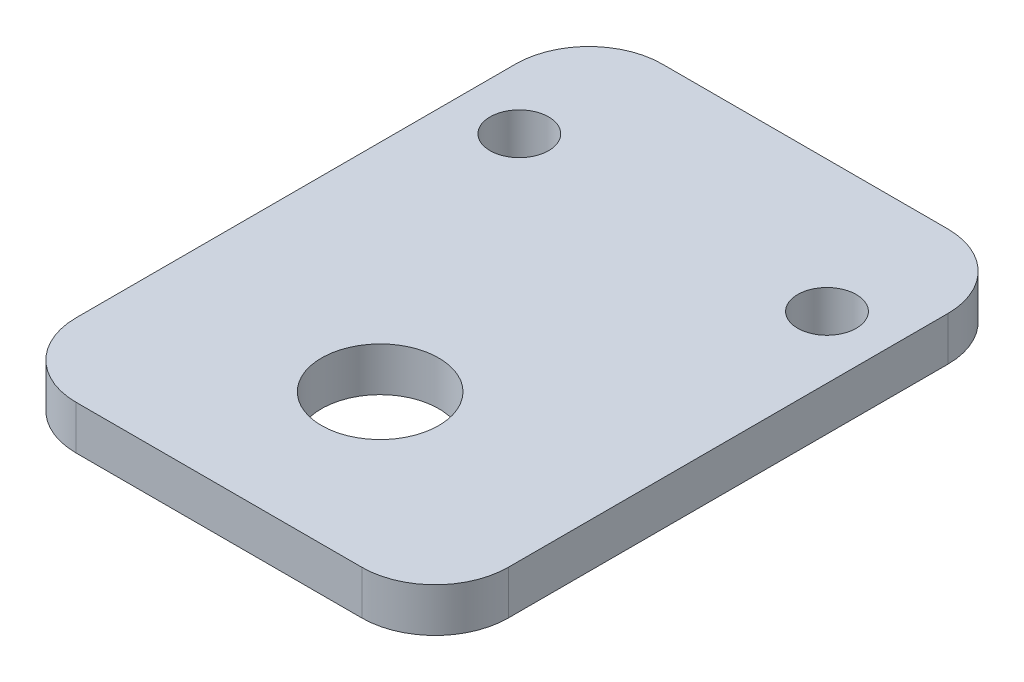
SolidWorks part; units mm, degrees
material "3.0205 (EN-AW 1200)"
ref_plane "Plan de face" through (0, 0, 0) normal (0, 0, 1) x (1, 0, 0)
ref_plane "Plan de dessus" through (0, 0, 0) normal (0, 1, 0) x (1, 0, 0)
ref_plane "Plan de droite" through (0, 0, 0) normal (1, 0, 0) x (0, 0, -1)
sketch "Esquisse1" plane through (0, 0, 0) normal (0, 0, 1) x (1, 0, 0)
  line L1 (0, 0) -> (29.5, 0)
  dimension "D2" = 29.5
extrude "Extru.-Mince1" add sketch "Esquisse1" along normal blind 40 thin thin type one direction reverse wall 3
sketch "Esquisse2" plane through (0, 3, 0) normal (0, 1, 0) x (1, 0, 0)
  line L0 (14.75, 0) -> (14.75, -29) construction
  line L1 (0, 0) -> (29.5, 0) construction
  circle A0 centre (4.25, -9) radius 2
  circle A1 centre (25.25, -9) radius 2
  circle A2 centre (14.75, -29) radius 4
  dimension "D1" = 8
  dimension "D2" = 20
  dimension "D3" = 9
  dimension "D4" = 21
  dimension "D5" = 4
extrude "Enlèv. mat.-Extru.1" cut sketch "Esquisse2" against normal through all
fillet "Congé1" radius 5 4 edges at (29.5, 1.5, 0) (0, 1.5, 40) (0, 1.5, 0) (29.5, 1.5, 40)
